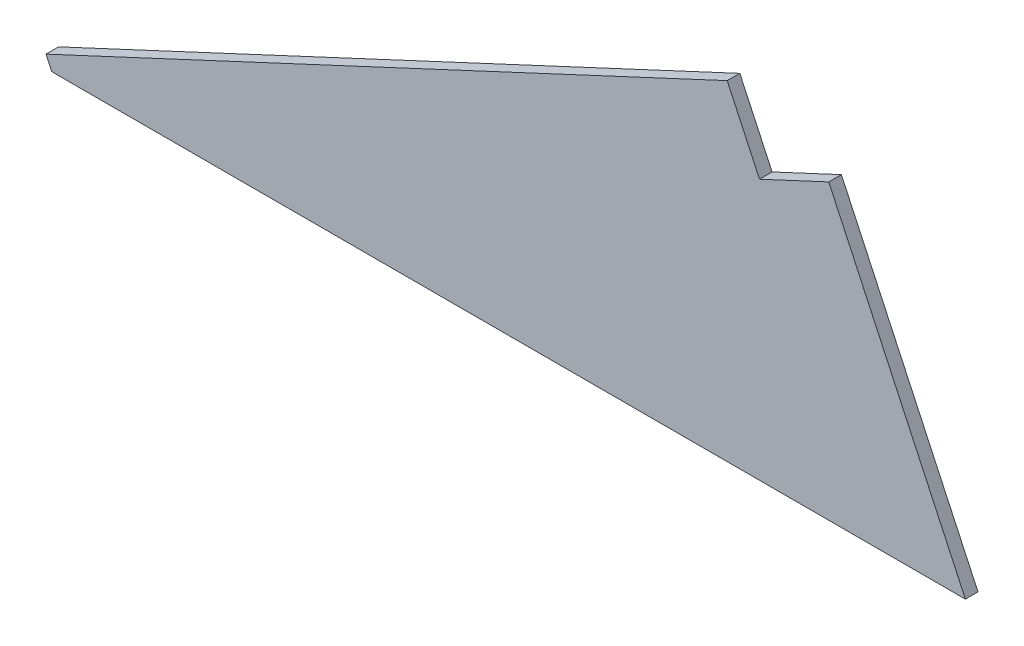
SolidWorks part; units mm, degrees
material "Balsa"
ref_plane "Front Plane" through (0, 0, 0) normal (0, 0, 1) x (1, 0, 0)
ref_plane "Top Plane" through (0, 0, 0) normal (0, 1, 0) x (1, 0, 0)
ref_plane "Right Plane" through (0, 0, 0) normal (1, 0, 0) x (0, 0, -1)
sketch "Sketch1" plane through (0, 0, 0) normal (0, 0, 1) x (1, 0, 0)
  line L0 (321.5462, 12.6346) -> (82.3833, 12.6346)
  line L1 (82.3833, 12.6346) -> (80.8781, 15.8625)
  line L2 (80.8781, 15.8625) -> (259.1989, 99.0148)
  line L3 (-63.4467, -51.4373) -> (255.5737, 97.3243) construction
  line L4 (259.1989, 99.0148) -> (267.6513, 80.8887)
  line L5 (267.6513, 80.8887) -> (285.7774, 89.341)
  line L6 (285.7774, 89.341) -> (321.5462, 12.6346)
  line L7 (327.4362, 0.0035) -> (398.701, -152.8244) construction
  line L8 (73.956, 12.6346) -> (314.6178, 12.6346) construction
  line L9 (285.7774, 89.341) -> (320.3088, 15.2883) construction
  line L10 (80.8781, 15.8625) -> (82.3833, 12.6346) construction
  point P13 (0, 0)
  point P14 (324.4201, 17.149)
  point P21 (81.6307, 14.2486)
  dimension "D1" = 20
  dimension "D2" = 20
extrude "Boss-Extrude1" add sketch "Sketch1" against normal blind 3.3
